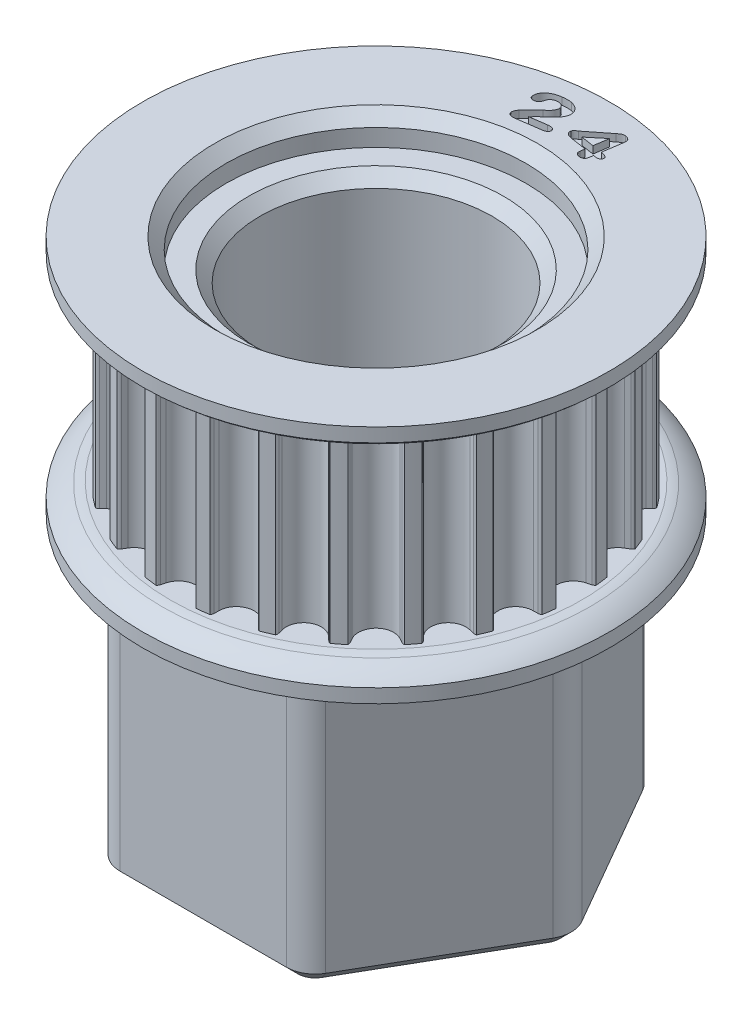
SolidWorks part; units mm, degrees
other "DetailItem2"
material "Markforged"
ref_plane "Front Plane" through (0, 0, 0) normal (0, 0, 1) x (1, 0, 0)
ref_plane "Top Plane" through (0, 0, 0) normal (0, 1, 0) x (1, 0, 0)
ref_plane "Right Plane" through (0, 0, 0) normal (1, 0, 0) x (0, 0, -1)
ref_axis "Centerline" through (0, 8.0264, 0) along (0, -1, 0)
sketch "Sketch1" plane through (0, 0, 0) normal (0, 1, 0) x (1, 0, 0)
  circle A0 centre (0, 0) radius 11.0782
  dimension "OuterDiameter" = 22.1563
extrude "ToothOD" add sketch "Sketch1" along normal mid plane 10.16
sketch "Sketch2" plane through (0, 0, 0) normal (0, 1, 0) x (1, 0, 0)
  line L0 (0, 9.9098) -> (50000, 9.9098) construction
  line L1 (0, 11.0782) -> (50000, 11.0782) construction
  line L2 (0, 0) -> (0, 50000) construction
  arc A0 (-0.937, 10.6282) -> (0, 9.9098) centre (0, 10.88) ccw
  arc A1 (-1.1005, 11.0234) -> (1.1005, 11.0234) centre (0, 0) cw
  circle A2 centre (0, 0) radius 11.0782 construction
  arc A3 (-0.937, 10.6282) -> (-1.0078, 10.88) centre (-11.9754, 7.6618) ccw
  arc A4 (-1.0078, 10.88) -> (-1.1005, 11.0234) centre (-1.2954, 10.7956) ccw
  circle A5 centre (0, 0) radius 11.0782 construction
  arc A6 (0.937, 10.6282) -> (1.0078, 10.88) centre (11.9754, 7.6618) cw
  arc A7 (1.0078, 10.88) -> (1.1005, 11.0234) centre (1.2954, 10.7956) cw
  arc A8 (0, 9.9098) -> (0.937, 10.6282) centre (0, 10.88) ccw
  dimension "D1" = 1.9406
  dimension "D3" = 22.86
  dimension "D4" = 0.5994
  dimension "D2" = 1.1684
  dimension "D5" = 1.2954
extrude "ToothProfile" cut sketch "Sketch2" against normal through all both and the other way through all
pattern_circular "ToothPattern" count 24 over 360 about axis through (0, 5.08, 0) along (0, -1, 0) of "ToothProfile"
sketch "Sketch4" plane through (0, 0, 0) normal (0, 0, 1) x (1, 0, 0)
  line L0 (0, -5.08) -> (11.3322, -5.08)
  line L1 (0, -6.604) -> (12.8562, -6.604)
  line L2 (0, -6.604) -> (0, -5.08)
  line L3 (12.8562, -6.604) -> (12.8562, -5.842)
  line L4 (0, 0) -> (50000, 0) construction
  line L5 (12.8562, 6.604) -> (12.8562, 5.842)
  line L6 (0, 6.604) -> (0, 5.08)
  line L7 (0, 6.604) -> (12.8562, 6.604)
  line L8 (0, 5.08) -> (11.3322, 5.08)
  arc A0 (11.3322, -5.08) -> (11.7872, -5.1726) centre (11.0525, -7.618) cw
  arc A2 (11.7872, -5.1726) -> (12.8562, -5.842) centre (10.6547, -8.1694) cw
  arc A3 (11.7872, 5.1726) -> (12.8562, 5.842) centre (10.6547, 8.1694) ccw
  arc A4 (11.3322, 5.08) -> (11.7872, 5.1726) centre (11.0525, 7.618) ccw
  dimension "D5" = 2.5534
  dimension "D6" = 3.2036
  dimension "FlangeID" = 11.3322
  dimension "FlangeOD" = 12.8562
  dimension "D1" = 1.524
  dimension "D2" = 0.762
  dimension "D3" = 5.08
  dimension "D4" = 13.208
  dimension "D7" = 0.762
  dimension "D8" = 0.6694
  dimension "D10" = 1.0689
revolve "Flange" add sketch "Sketch4" angle 360 about axis through (0, 8.0264, 0) along (0, -1, 0)
sketch "Sketch6" plane through (0, 0, 0) normal (0, 0, 1) x (1, 0, 0)
  line L0 (0, -6.604) -> (0, -7.9375) construction
  line L1 (-12.8562, -6.604) -> (12.8562, -6.604) construction
  line L2 (0, -7.9375) -> (8.2931, -7.9375) construction
  line L3 (8.2931, -7.9375) -> (8.2931, -6.604) construction
  line L4 (8.2931, -6.604) -> (0, -6.604) construction
  line L5 (0, 0) -> (50000, 0) construction
  line L6 (8.2931, 6.604) -> (0, 6.604)
  line L7 (8.2931, 7.9375) -> (8.2931, 6.604)
  line L8 (0, 7.9375) -> (8.2931, 7.9375)
  line L9 (0, 6.604) -> (0, 7.9375)
  line L11 (36.0254, 12.0878) -> (29.4657, 15.4613) construction
  line L12 (29.4657, 15.4613) -> (23.2643, 11.4672) construction
  line L13 (23.2643, 11.4672) -> (23.6226, 4.0996) construction
  line L14 (23.6226, 4.0996) -> (30.1823, 0.7261) construction
  line L15 (30.1823, 0.7261) -> (36.3837, 4.7202) construction
  line L16 (36.3837, 4.7202) -> (36.0254, 12.0878) construction
  circle A0 centre (29.824, 8.0937) radius 6.3881 construction
  circle A1 centre (29.824, 8.0937) radius 8.2931 construction
  dimension "D2" = 12.7762
  dimension "D1" = 15.875
  dimension "D4" = 8.2931
  dimension "D3" = 1.905
  dimension "D5" = 1.3335
revolve "TopBearingBoss" [suppressed] add sketch "Sketch6" angle 360 about axis through (0, 8.0264, 0) along (0, -1, 0)
mirror "BottomBearingBoss" [suppressed] about plane through (0, 0, 0) normal (0, 1, 0)
sketch "Sketch7" plane through (0, 0, 0) normal (0, -1, 0) x (1, 0, 0)
  line L1 (3.6882, 6.3881) -> (-3.6882, 6.3881) construction
  line L2 (-3.6882, 6.3881) -> (-7.3763, 0) construction
  line L3 (-7.3763, 0) -> (-3.6882, -6.3881) construction
  line L4 (-3.6882, -6.3881) -> (3.6882, -6.3881) construction
  line L5 (3.6882, -6.3881) -> (7.3763, 0) construction
  line L6 (7.3763, 0) -> (3.6882, 6.3881) construction
  circle A0 centre (0, 0) radius 6.3881
  dimension "HexBoreDi," = 12.7762
extrude "Bore" cut sketch "Sketch7" against normal through all both and the other way through all
sketch "Sketch9" plane through (0, 6.604, 0) normal (0, 1, 0) x (1, 0, 0)
  arc A0 (-6.4927, -6.4927) -> (6.4927, -6.4927) centre (0, 0) cw construction
  text T0 "24" font "Arial Rounded MT Bold" height 4.572
  point P3 (0, 9.1821)
  dimension "D1" = 9.1821
  dimension "D2" = 270
extrude "Large Tooth Count" [suppressed] cut sketch "Sketch9" against normal blind 0.4 and the other way through all
sketch "Sketch11" plane through (0, 6.604, 0) normal (0, 1, 0) x (1, 0, 0)
  arc A0 (-6.8456, -6.8456) -> (6.8456, -6.8456) centre (0, 0) cw construction
  circle A1 centre (0, 0) radius 12.8562 construction
  text T0 "<b>24</b>" font "Arial Rounded MT Bold" height 2.286
  point P6 (0, 9.6812)
  dimension "D1" = 3.175
  dimension "D3" = 270
extrude "Small Tooth Count" cut sketch "Sketch11" against normal blind 0.4 and the other way through all
sketch "Sketch12" plane through (0, -6.604, 0) normal (0, -1, 0) x (1, 0, 0)
  line L1 (5.4993, -9.525) -> (10.9985, 0)
  line L2 (10.9985, 0) -> (5.4993, 9.525)
  line L3 (5.4993, 9.525) -> (-5.4993, 9.525)
  line L4 (-5.4993, 9.525) -> (-10.9985, 0)
  line L5 (-10.9985, 0) -> (-5.4993, -9.525)
  line L6 (-5.4993, -9.525) -> (5.4993, -9.525)
  circle A0 centre (0, 0) radius 6.3881 construction
  circle A1 centre (0, 0) radius 6.3881
  circle A2 centre (0, 0) radius 9.525 construction
  dimension "D1" = 19.05
extrude "Boss-Extrude1" add sketch "Sketch12" along normal blind 15.24
sketch "Sketch27" plane through (0, 6.604, 0) normal (0, 1, 0) x (1, 0, 0)
  circle A0 centre (0, 0) radius 8.255
  dimension "D1" = 16.51
extrude "Cut-Extrude1" cut sketch "Sketch27" against normal blind 1.5875
fillet "Fillet1" radius 1.5875 6 edges at (-5.4993, -14.224, 9.525) (5.4993, -14.224, 9.525) (10.9985, -14.224, 0) (5.4993, -14.224, -9.525) (-10.9985, -14.224, 0) (-5.4993, -14.224, -9.525)
sketch "Sketch25" plane through (0, -6.604, 0) normal (0, -1, 0) x (1, 0, 0)
  line L6 (-4.5827, -9.525) -> (4.5827, -9.525)
  line L7 (-10.5403, -0.7937) -> (-5.9575, -8.7313)
  line L8 (-5.9575, 8.7312) -> (-10.5403, 0.7938)
  line L9 (4.5827, 9.525) -> (-4.5827, 9.525)
  line L10 (10.5403, 0.7938) -> (5.9575, 8.7312)
  line L11 (5.9575, -8.7312) -> (10.5403, -0.7937)
  line L12 (-4.5827, -9.525) -> (4.5827, -9.525)
  line L13 (-10.5403, -0.7937) -> (-5.9575, -8.7313)
  line L14 (-5.9575, 8.7312) -> (-10.5403, 0.7938)
  line L15 (4.5827, 9.525) -> (-4.5827, 9.525)
  line L16 (10.5403, 0.7938) -> (5.9575, 8.7312)
  line L17 (5.9575, -8.7312) -> (10.5403, -0.7937)
  arc A6 (-5.9575, -8.7313) -> (-4.5827, -9.525) centre (-4.5827, -7.9375) ccw
  arc A7 (-10.5403, 0.7938) -> (-10.5403, -0.7937) centre (-9.1654, 0) ccw
  arc A8 (-4.5827, 9.525) -> (-5.9575, 8.7312) centre (-4.5827, 7.9375) ccw
  arc A9 (5.9575, 8.7312) -> (4.5827, 9.525) centre (4.5827, 7.9375) ccw
  arc A10 (10.5403, -0.7937) -> (10.5403, 0.7938) centre (9.1654, 0) ccw
  arc A11 (4.5827, -9.525) -> (5.9575, -8.7312) centre (4.5827, -7.9375) ccw
  arc A12 (-5.9575, -8.7313) -> (-4.5827, -9.525) centre (-4.5827, -7.9375) ccw
  arc A13 (-10.5403, 0.7938) -> (-10.5403, -0.7937) centre (-9.1654, 0) ccw
  arc A14 (-4.5827, 9.525) -> (-5.9575, 8.7312) centre (-4.5827, 7.9375) ccw
  arc A15 (5.9575, 8.7312) -> (4.5827, 9.525) centre (4.5827, 7.9375) ccw
  arc A16 (10.5403, -0.7937) -> (10.5403, 0.7938) centre (9.1654, 0) ccw
  arc A17 (4.5827, -9.525) -> (5.9575, -8.7312) centre (4.5827, -7.9375) ccw
  dimension "D1" = 0
sweep "Cut-Sweep1" cut path "Sketch25" circular profile diameter 0.635 parameters "D3"=0.635
fillet "Fillet2" radius 1.27 24 edges at (-5.5352, -6.604, 9.5873) (0, -6.604, 9.8425) (5.5352, -6.604, 9.5873) (8.5239, -6.604, 4.9213) (11.0704, -6.604, 0) (8.5239, -6.604, -4.9212) (5.5352, -6.604, -9.5873) (0, -6.604, -9.8425) (-5.5352, -6.604, -9.5873) (-8.5239, -6.604, -4.9213) (-11.0704, -6.604, 0) (-10.7529, -6.9215, 0) (-8.2489, -6.9215, -4.7625) (-5.3765, -6.9215, -9.3123) (0, -6.9215, -9.525) (5.3765, -6.9215, -9.3123) (8.2489, -6.9215, -4.7625) (10.7529, -6.9215, 0) (8.2489, -6.9215, 4.7625) (5.3765, -6.9215, 9.3123) (0, -6.9215, 9.525) (-5.3765, -6.9215, 9.3123) (-8.5239, -6.604, 4.9212) (-8.2489, -6.9215, 4.7625)
chamfer "Chamfer1" distance 0.635 angle 45 3 edges at (0, -21.844, -6.3881) (0, 6.604, 8.255) (0, 5.0165, 6.3881)
chamfer "Chamfer2" distance 0.635 angle 45 12 edges at (0, -21.844, -9.525) (5.3765, -21.844, -9.3123) (-5.3765, -21.844, -9.3123) (8.2489, -21.844, -4.7625) (-8.2489, -21.844, -4.7625) (10.7529, -21.844, 0) (-10.7529, -21.844, 0) (8.2489, -21.844, 4.7625) (-8.2489, -21.844, 4.7625) (5.3765, -21.844, 9.3123) (-5.3765, -21.844, 9.3123) (0, -21.844, 9.525)
equation "\"OuterDiameter@Sketch1\"= \"OD\""
equation "\"Teeth\"= \"No_Teeth\""
equation "\"PD\"= \"No_Teeth\" * 3mm / pi"
equation "\"OD\"= \"PD\" - .030"
equation "\"ToothCount@ToothPattern\" = \"Teeth\""
equation "\"Angle\"= 360 / \"Teeth\""
equation "\"AngleSpacing@ToothPattern\" = \"Angle\""
equation "\"FlangeID@Sketch4\"=\"OD\"/2+.01"
equation "\"FlangeOD@Sketch4\"=\"PD\"/2+.055"
equation "\"D3@Sketch4\"=\"Tooth_Face_Length\"/2"
equation "\"Bearing_Feature\"= \"Bearing_Boss\""
equation "\"TopBearingBoss\" = IIF ( \"Bearing_Feature\" > 0 , \"unsuppressed\" , \"suppressed\" )"
equation "\"HexBore\"= \"Hex_Bore\" + \"Print_Tolerance\""
equation "\"HexBoreDi,@Sketch7\"= \"HexBore\""
equation "\"D2@Sketch6\"=\"HexBore\""
equation "\"D4@Sketch6\"=\"HexBore\"/2+.075"
equation "\"Large Tooth Count\" = iif ( \"No_Teeth\" < \"TextTooth\" , \"suppressed\" , \"unsuppressed\" )"
equation "\"Small Tooth Count\"= iif ( \"No_Teeth\" < \"TextTooth\" , \"unsuppressed\" , \"suppressed\" )"
equation "\"BottomBearingBoss\" = iif ( \"Bearing_Feature\" > 1 , \"unsuppressed\" , \"suppressed\" )"
equation "\"ToothFaceLength@ToothOD\" = \"Tooth_Face_Length\""
equation "\"D4@Sketch4\" = \"Width_No_BearingBoss\""
equation "\"D1@Sketch9\"=\"HexBore\"/2+.11"
equation "\"TextTooth\"= iif ( \"Hex_Bore\" <= .380 , 23 , iif ( \"Hex_Bore\" <= .505 , 25 , 16 ) )"
equation "\"D1@Sketch6\"=\"Overall_Width\""
